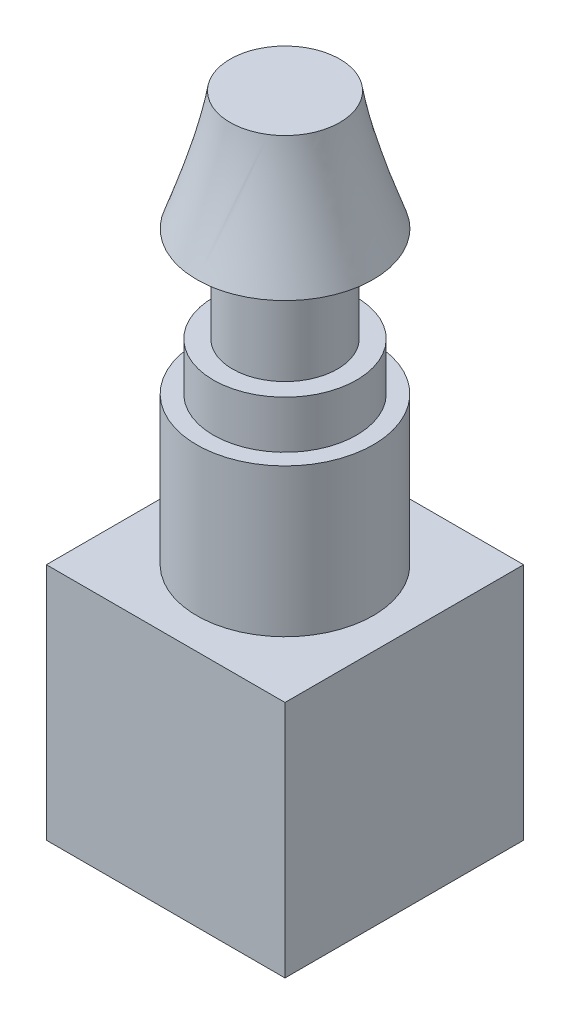
SolidWorks part; units mm, degrees
ref_plane "Front Plane" through (0, 0, 0) normal (0, 0, 1) x (1, 0, 0)
ref_plane "Top Plane" through (0, 0, 0) normal (0, 1, 0) x (1, 0, 0)
ref_plane "Right Plane" through (0, 0, 0) normal (1, 0, 0) x (0, 0, -1)
sketch "Sketch1" plane through (0, 0, 0) normal (0, 1, 0) x (1, 0, 0)
  circle A0 centre (0, 0) radius 1.85
  dimension "D1" = 3.7
extrude "Boss-Extrude1" add sketch "Sketch1" along normal blind 3.1
sketch "Sketch2" plane through (0, 3.1, 0) normal (0, 1, 0) x (1, 0, 0)
  circle A0 centre (0, 0) radius 1.5
  dimension "D1" = 3
extrude "Boss-Extrude2" add sketch "Sketch2" along normal blind 1
sketch "Sketch3" plane through (0, 4.1, 0) normal (0, 1, 0) x (1, 0, 0)
  circle A0 centre (0, 0) radius 1.1
  dimension "D1" = 2.2
extrude "Boss-Extrude3" add sketch "Sketch3" along normal blind 2
sketch "Sketch4" plane through (0, 6.1, 0) normal (0, 1, 0) x (1, 0, 0)
  circle A0 centre (0, 0) radius 1.85
  dimension "D1" = 3.7
ref_plane "Plane1" through (0, 8.6, 0) normal (0, 1, 0) x (1, 0, 0)
sketch "Sketch5" plane through (0, 8.6, 0) normal (0, 1, 0) x (1, 0, 0)
  circle A0 centre (0, 0) radius 1.15
  dimension "D1" = 2.3
loft "Loft1" add profiles "Sketch4", "Sketch5" connector at (0, 6.1, 1.85) connector at (0.6205, 8.6, 0.9683)
sketch "Sketch6" plane through (0, 0, 0) normal (0, -1, 0) x (1, 0, 0)
  line L1 (-2.5, 2.5) -> (2.5, 2.5)
  line L2 (-2.5, 2.5) -> (-2.5, -2.5)
  line L3 (-2.5, -2.5) -> (2.5, -2.5)
  line L4 (2.5, 2.5) -> (2.5, -2.5)
  line L5 (-2.5, 2.5) -> (2.5, -2.5) construction
  line L6 (-2.5, -2.5) -> (2.5, 2.5) construction
  point P0 (0, 0)
  dimension "D1" = 5
  dimension "D2" = 5
extrude "Boss-Extrude4" add sketch "Sketch6" along normal blind 5
